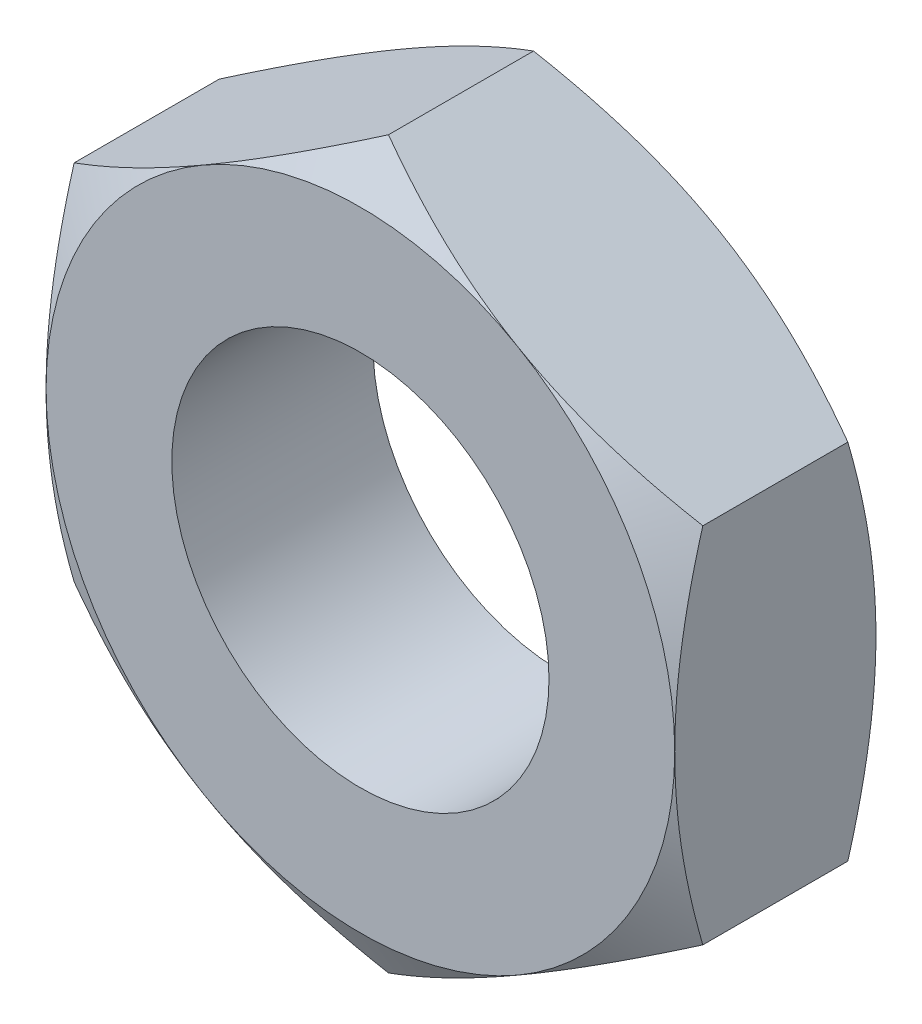
SolidWorks part; units mm, degrees
ref_plane "Plan1" through (0, 0, 0) normal (0, 0, 1) x (1, 0, 0)
ref_plane "Plan2" through (0, 0, 0) normal (0, 1, 0) x (1, 0, 0)
ref_plane "Plan3" through (0, 0, 0) normal (1, 0, 0) x (0, 0, -1)
sketch "Esquisse1" plane through (0, 0, 0) normal (0, 0, 1) x (1, 0, 0)
  line L0 (0, 0) -> (5, 0) construction
  line L1 (5, -2.8868) -> (5, 2.8868)
  line L2 (0, 0) -> (5, 2.8868) construction
  line L3 (0, 0) -> (0, 5.7735) construction
  line L4 (5, 2.8868) -> (0, 5.7735)
  line L5 (5, -2.8868) -> (0, -5.7735)
  line L6 (-5, -2.8868) -> (0, -5.7735)
  line L7 (-5, -2.8868) -> (-5, 2.8868)
  line L8 (-5, 2.8868) -> (0, 5.7735)
  circle A0 centre (0, 0) radius 5 construction
  circle A1 centre (0, 0) radius 5.7735 construction
  dimension "D2" = 10
  dimension "D1" = 30
extrude "Base-Extrusion" add sketch "Esquisse1" against normal blind 3.2
sketch "Esquisse2" plane through (0, 0, 0) normal (0, 1, 0) x (1, 0, 0)
  line L0 (-5, 0) -> (-8.7713, 0)
  line L1 (0, 3.2) -> (0, 0) construction
  line L2 (-5, 3.2) -> (-8.7713, 3.2)
  line L3 (-8.7713, 3.2) -> (-8.7713, 0)
  line L5 (-7.7713, 1.6) -> (-5, 3.2)
  line L6 (0, 3.2) -> (0, 0) construction
  line L7 (-5, 0) -> (-7.7713, 1.6)
  dimension "D1" = 30
  dimension "D2" = 1
  dimension "D3" = 30
revolve "Enlèvement de matière-Révolution1" cut sketch "Esquisse2" angle 360 about L6
sketch "Esquisse3" plane through (0, 0, 0) normal (0, 0, 1) x (1, 0, 0)
  circle A0 centre (0, 0) radius 3
  dimension "D1" = 6
extrude "Enlèv. mat.-Extru.1" cut sketch "Esquisse3" against normal through all
ref_axis "Axe1" through (0, 0, -50) along (0, 0, 1)
